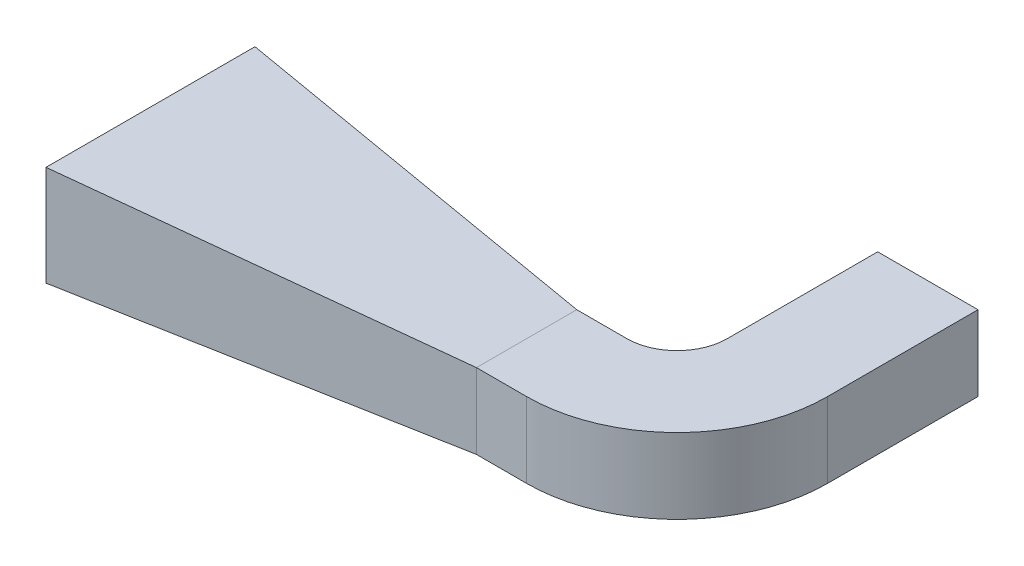
SolidWorks part; units mm, degrees
ref_plane "前视基准面" through (0, 0, 0) normal (0, 0, 1) x (1, 0, 0)
ref_plane "上视基准面" through (0, 0, 0) normal (0, 1, 0) x (1, 0, 0)
ref_plane "右视基准面" through (0, 0, 0) normal (1, 0, 0) x (0, 0, -1)
other "Configuration Table"
sketch "草图1" plane through (0, 0, 0) normal (1, 0, 0) x (0, 0, -1)
  line L1 (-250, 120) -> (250, 120)
  line L2 (-250, 120) -> (-250, -120)
  line L3 (-250, -120) -> (250, -120)
  line L4 (250, 120) -> (250, -120)
  line L5 (-250, 120) -> (250, -120) construction
  line L6 (-250, -120) -> (250, 120) construction
  point P0 (0, 0)
  dimension "D1" = 500
  dimension "D2" = 240
ref_plane "基准面1" through (900, 0, 0) normal (1, 0, 0) x (0, 0, -1)
sketch "草图2" plane through (900, 0, 0) normal (1, 0, 0) x (0, 0, -1)
  line L1 (-120, 90) -> (120, 90)
  line L2 (-120, 90) -> (-120, -90)
  line L3 (-120, -90) -> (120, -90)
  line L4 (120, 90) -> (120, -90)
  line L5 (-120, 90) -> (120, -90) construction
  line L6 (-120, -90) -> (120, 90) construction
  point P0 (0, 0)
  point P6 (0, 0)
  dimension "D1" = 240
  dimension "D2" = 180
loft "放样1" add profiles "草图2", "草图1" connector at (900, 90, 120) connector at (0, 120, 250)
ref_plane "基准面2" through (0, 0, 0) normal (0, 1, 0) x (1, 0, 0)
extrude "凸台-拉伸2" add sketch "草图2<5>" along normal blind 120
sketch "草图2<5>" plane through (900, 0, 0) normal (1, 0, 0) x (0, 0, -1) same geometry as "草图2"
ref_plane "基准面4" through (1020, 0, 0) normal (1, 0, 0) x (0, 0, -1)
sketch "草图10" plane through (1020, 0, 0) normal (1, 0, 0) x (0, 0, -1)
  line L0 (120, 90) -> (120, -90) construction
  line L1 (-120, -90) -> (120, -90) construction
  line L2 (-120, 90) -> (-120, -90) construction
  line L3 (-120, 90) -> (120, 90) construction
  line L4 (120, 90) -> (120, -90)
  line L5 (-120, -90) -> (120, -90)
  line L6 (-120, 90) -> (-120, -90)
  line L7 (-120, 90) -> (120, 90)
  line L8 (240, 90) -> (240, -126.9882) construction
  dimension "D1" = 240
revolve "旋转2" add sketch "草图10" angle 90 about L8 reverse direction yes
ref_plane "基准面5" through (0, 0, -240) normal (0, 0, -1) x (-1, 0, 0)
sketch "草图11" plane through (0, 0, -240) normal (0, 0, -1) x (-1, 0, 0)
  line L0 (-1140, -90) -> (-1140, 90) construction
  line L1 (-1380, -90) -> (-1140, -90) construction
  line L2 (-1380, 90) -> (-1380, -90) construction
  line L3 (-1140, 90) -> (-1380, 90) construction
  line L4 (-1140, -90) -> (-1140, 90)
  line L5 (-1380, -90) -> (-1140, -90)
  line L6 (-1380, 90) -> (-1380, -90)
  line L7 (-1140, 90) -> (-1380, 90)
extrude "凸台-拉伸3" add sketch "草图11" along normal blind 360
ref_plane "基准面6" through (0, 0, 0) normal (-1, 0, 0) x (0, 0, 1)
sketch "草图13" plane through (0, 0, 0) normal (-1, 0, 0) x (0, 0, 1)
  line L0 (-250, -120) -> (-250, 120) construction
  line L1 (250, -120) -> (-250, -120) construction
  line L2 (250, 120) -> (250, -120) construction
  line L3 (-250, 120) -> (250, 120) construction
  line L4 (-250, -120) -> (-250, 120) construction
  line L5 (250, -120) -> (-250, -120) construction
  line L6 (250, 120) -> (250, -120) construction
  line L7 (-250, 120) -> (250, 120) construction
  circle A0 centre (225, -100) radius 7.5
  circle A1 centre (175, -100) radius 7.5
  circle A2 centre (125, -100) radius 7.5
  circle A3 centre (75, -100) radius 7.5
  circle A4 centre (25, -100) radius 7.5
  circle A5 centre (-25, -100) radius 7.5
  circle A6 centre (-75, -100) radius 7.5
  circle A7 centre (-125, -100) radius 7.5
  circle A8 centre (-175, -100) radius 7.5
  circle A9 centre (-225, -100) radius 7.5
  circle A10 centre (175, -50) radius 7.5
  circle A11 centre (125, -50) radius 7.5
  circle A12 centre (75, -50) radius 7.5
  circle A13 centre (25, -50) radius 7.5
  circle A14 centre (-25, -50) radius 7.5
  circle A15 centre (-75, -50) radius 7.5
  circle A16 centre (-125, -50) radius 7.5
  circle A17 centre (-175, -50) radius 7.5
  circle A18 centre (-225, -50) radius 7.5
  circle A19 centre (175, 0) radius 7.5
  circle A20 centre (125, 0) radius 7.5
  circle A21 centre (75, 0) radius 7.5
  circle A22 centre (25, 0) radius 7.5
  circle A23 centre (-25, 0) radius 7.5
  circle A24 centre (-75, 0) radius 7.5
  circle A25 centre (-125, 0) radius 7.5
  circle A26 centre (-175, 0) radius 7.5
  circle A27 centre (-225, 0) radius 7.5
  circle A28 centre (175, 50) radius 7.5
  circle A29 centre (125, 50) radius 7.5
  circle A30 centre (75, 50) radius 7.5
  circle A31 centre (25, 50) radius 7.5
  circle A32 centre (-25, 50) radius 7.5
  circle A33 centre (-75, 50) radius 7.5
  circle A34 centre (-125, 50) radius 7.5
  circle A35 centre (-175, 50) radius 7.5
  circle A36 centre (-225, 50) radius 7.5
  circle A37 centre (175, 100) radius 7.5
  circle A38 centre (125, 100) radius 7.5
  circle A39 centre (75, 100) radius 7.5
  circle A40 centre (25, 100) radius 7.5
  circle A41 centre (-25, 100) radius 7.5
  circle A42 centre (-75, 100) radius 7.5
  circle A43 centre (-125, 100) radius 7.5
  circle A44 centre (-175, 100) radius 7.5
  circle A45 centre (-225, 100) radius 7.5
  circle A46 centre (225, -50) radius 7.5
  circle A47 centre (225, 0) radius 7.5
  circle A48 centre (225, 50) radius 7.5
  circle A49 centre (225, 100) radius 7.5
  dimension "D1" = 15
  dimension "D2" = 25
  dimension "D3" = 20
  dimension "D4" = 10
  dimension "D5" = 5
extrude "凸台-拉伸4" add sketch "草图13" along normal blind 10
